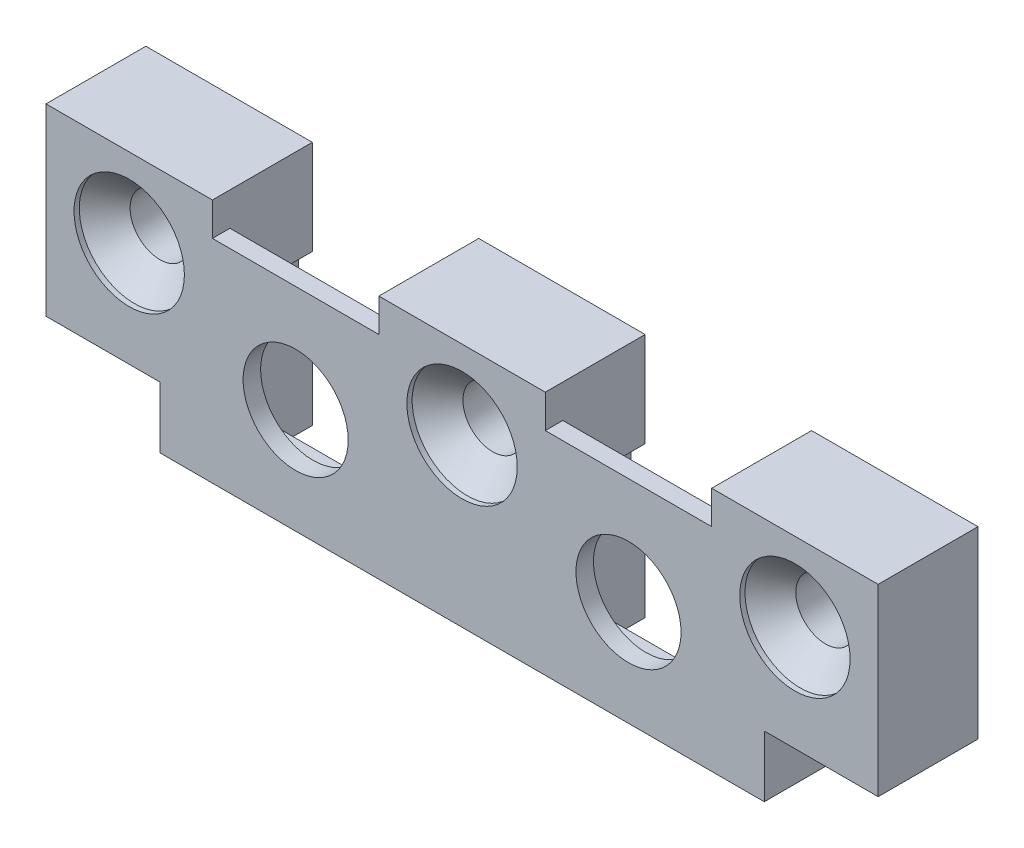
SolidWorks part; units mm, degrees
ref_plane "Front Plane" through (0, 0, 0) normal (0, 0, 1) x (1, 0, 0)
ref_plane "Top Plane" through (0, 0, 0) normal (0, 1, 0) x (1, 0, 0)
ref_plane "Right Plane" through (0, 0, 0) normal (1, 0, 0) x (0, 0, -1)
sketch "Sketch1" plane through (0, 0, 0) normal (0, 0, 1) x (1, 0, 0)
  line L0 (-54.75, 14) -> (-64.25, 14)
  line L1 (-81, 14) -> (-54.75, 14) construction
  line L2 (-64.25, 14) -> (-64.25, 0)
  line L3 (-3, 0) -> (-26.25, 0) construction
  line L4 (-64.25, 0) -> (-54.75, 0)
  line L5 (-16.75, 0) -> (-16.75, 14)
  line L6 (-26.25, 14) -> (0, 14) construction
  line L7 (-16.75, 14) -> (-26.25, 14)
  line L8 (-26.25, 14) -> (-26.25, 8.6)
  line L9 (-26.25, 8.6) -> (-25.45, 8.6)
  line L10 (-25.45, 8.6) -> (-25.45, 4.6)
  line L11 (-25.45, 4.6) -> (-26.25, 4.6)
  line L12 (-26.25, 4.6) -> (-26.25, 0)
  line L14 (-35.75, 0) -> (-35.75, 4.6)
  line L15 (-35.75, 4.6) -> (-36.55, 4.6)
  line L16 (-36.55, 4.6) -> (-36.55, 8.6)
  line L17 (-36.55, 8.6) -> (-35.75, 8.6)
  line L18 (-35.75, 8.6) -> (-35.75, 14)
  line L19 (-35.75, 14) -> (-45.25, 14)
  line L20 (-45.25, 14) -> (-45.25, 8.6)
  line L21 (-45.25, 8.6) -> (-44.45, 8.6)
  line L22 (-44.45, 8.6) -> (-44.45, 4.6)
  line L23 (-44.45, 4.6) -> (-45.25, 4.6)
  line L24 (-45.25, 4.6) -> (-45.25, 0)
  line L26 (-54.75, 0) -> (-54.75, 4.6)
  line L27 (-54.75, 4.6) -> (-55.55, 4.6)
  line L28 (-55.55, 4.6) -> (-55.55, 8.6)
  line L29 (-55.55, 8.6) -> (-54.75, 8.6)
  line L30 (-54.75, 8.6) -> (-54.75, 14)
  line L31 (-45.25, 0) -> (-35.75, 0)
  line L32 (-26.25, 0) -> (-16.75, 0)
  circle A0 centre (-40.5, 9.5) radius 1.5
  circle A1 centre (-21.5, 9.5) radius 1.5
  circle A2 centre (-59.5, 9.5) radius 1.5
  dimension "D1" = 0.8
  dimension "D2" = 9.5
extrude "Boss-Extrude1" add sketch "Sketch1" along normal up to surface (1.2 mm away) contours L29 L30 L0 L2 L4 L26 L27 L28 A2 | L24 L31 L14 L15 L16 L17 L18 L19 L20 L21 L22 L23 A0 | L12 L32 L5 L7 L8 L9 L10 L11 A1 region at (-59.6134, 6.8664, 0) region at (-21.3866, 6.8664, 0) region at (-40.5, 6.8736, 0)
sketch "Sketch2" plane through (0, 0, 1.2) normal (0, 0, 1) x (1, 0, 0)
  line L0 (-54.75, 14) -> (-64.25, 14)
  line L1 (-64.25, 14) -> (-64.25, 0)
  line L2 (-64.25, 0) -> (-16.75, 0)
  line L3 (-16.75, 0) -> (-16.75, 14)
  line L4 (-16.75, 14) -> (-26.25, 14)
  line L10 (-26.25, 1.1) -> (-35.75, 1.1)
  line L16 (-35.75, 14) -> (-45.25, 14)
  line L22 (-45.25, 1.1) -> (-54.75, 1.1)
  line L28 (-54.75, 14) -> (-54.75, 1.1)
  line L29 (-45.25, 14) -> (-45.25, 1.1)
  line L30 (-35.75, 14) -> (-35.75, 1.1)
  line L31 (-26.25, 14) -> (-26.25, 1.1)
  line L32 (-47.25, 1.1) -> (-52.75, 1.1) construction
  circle A0 centre (-59.5, 9.5) radius 1.5
  circle A1 centre (-40.5, 9.5) radius 1.5
  circle A2 centre (-21.5, 9.5) radius 1.5
extrude "Boss-Extrude2" add sketch "Sketch2" along normal up to surface (3.5 mm away)
sketch "Sketch3" plane through (0, 0, 4.7) normal (0, 0, 1) x (1, 0, 0)
  line L0 (-64.25, 14) -> (-54.75, 14)
  line L1 (-54.75, 14) -> (-54.75, 12.1)
  line L2 (-54.75, 12.1) -> (-45.25, 12.1)
  line L3 (-45.25, 12.1) -> (-45.25, 14)
  line L4 (-45.25, 14) -> (-35.75, 14)
  line L5 (-35.75, 14) -> (-35.75, 12.1)
  line L6 (-35.75, 12.1) -> (-26.25, 12.1)
  line L7 (-26.25, 12.1) -> (-26.25, 14)
  line L8 (-26.25, 14) -> (-16.75, 14)
  line L9 (-16.75, 14) -> (-16.75, 0)
  line L10 (-16.75, 0) -> (-64.25, 0)
  line L11 (-64.25, 0) -> (-64.25, 14)
  line L12 (-64.25, 0) -> (-16.75, 0) construction
  circle A0 centre (-59.5, 9.5) radius 1.5
  circle A1 centre (-40.5, 9.5) radius 1.5
  circle A2 centre (-21.5, 9.5) radius 1.5
extrude "Boss-Extrude3" add sketch "Sketch3" along normal blind 1
hole_wizard "CSK for M3 Countersunk Flat Head Screw1" positions "Sketch4" profile "Sketch6" countersink size "M3" standard "ISO" end condition through all
sketch "Sketch4" plane through (0, 0, 5.7) normal (0, 0, 1) x (1, 0, 0)
  point P0 (-59.5, 9.5)
  point P3 (-59.5, 9.5)
  point P6 (-40.5, 9.5)
  point P9 (-21.5, 9.5)
sketch "Sketch6" plane through (-59.5, 9.5, 5.7) normal (1, 0, 0) x (0, -1, 0)
  line L0 (0, 0) -> (0, 5.7)
  line L1 (0, 5.7) -> (1.7, 5.7)
  line L2 (1.7, 5.7) -> (1.7, 1.75)
  line L3 (1.7, 1.75) -> (3.15, 0.3)
  line L4 (3.15, 0.3) -> (3.15, 0)
  line L6 (3.15, 0) -> (0, 0)
  line L7 (-1.7, 1.75) -> (-3.15, 0.3) construction
  line L11 (0, -6.35) -> (0, 107.95) construction
  dimension "Thru Hole Dia." = 3.4
  dimension "Thru Hole Depth" = 5.7
  dimension "C'Sink Dia." = 6.3
  dimension "C'Sink Angle" = 90
  dimension "Head Clearance" = 0.3
sketch "Sketch7" plane through (0, 0, 5.7) normal (0, 0, 1) x (1, 0, 0)
  circle A0 centre (-50, 6) radius 3
  circle A1 centre (-31, 6) radius 3
  dimension "D1" = 6
extrude "Cut-Extrude1" cut sketch "Sketch7" against normal through all
sketch "Sketch8" plane through (0, 0, 5.7) normal (0, 0, 1) x (1, 0, 0)
  line L1 (-64.25, 0) -> (-57.75, 0)
  line L2 (-64.25, 0) -> (-64.25, 3.5)
  line L3 (-64.25, 3.5) -> (-57.75, 3.5)
  line L4 (-57.75, 0) -> (-57.75, 3.5)
  line L5 (-16.75, 0) -> (-23.25, 0)
  line L6 (-16.75, 0) -> (-16.75, 3.5)
  line L7 (-16.75, 3.5) -> (-23.25, 3.5)
  line L8 (-23.25, 0) -> (-23.25, 3.5)
  dimension "D1" = 34.5
  dimension "D2" = 3.5
extrude "Cut-Extrude2" cut sketch "Sketch8" against normal through all
sketch "Sketch10" plane through (0, 0, 1.2) normal (0, 0, -1) x (-1, 0, 0)
  line L1 (26.25, 1.1) -> (35.75, 1.1)
  line L2 (26.25, 1.1) -> (26.25, 0)
  line L3 (26.25, 0) -> (35.75, 0)
  line L4 (35.75, 1.1) -> (35.75, 0)
  line L5 (45.25, 0) -> (54.75, 0)
  line L6 (45.25, 0) -> (45.25, 1.1)
  line L7 (45.25, 1.1) -> (54.75, 1.1)
  line L8 (54.75, 0) -> (54.75, 1.1)
extrude "Cut-Extrude3" cut sketch "Sketch10" against normal blind 1
